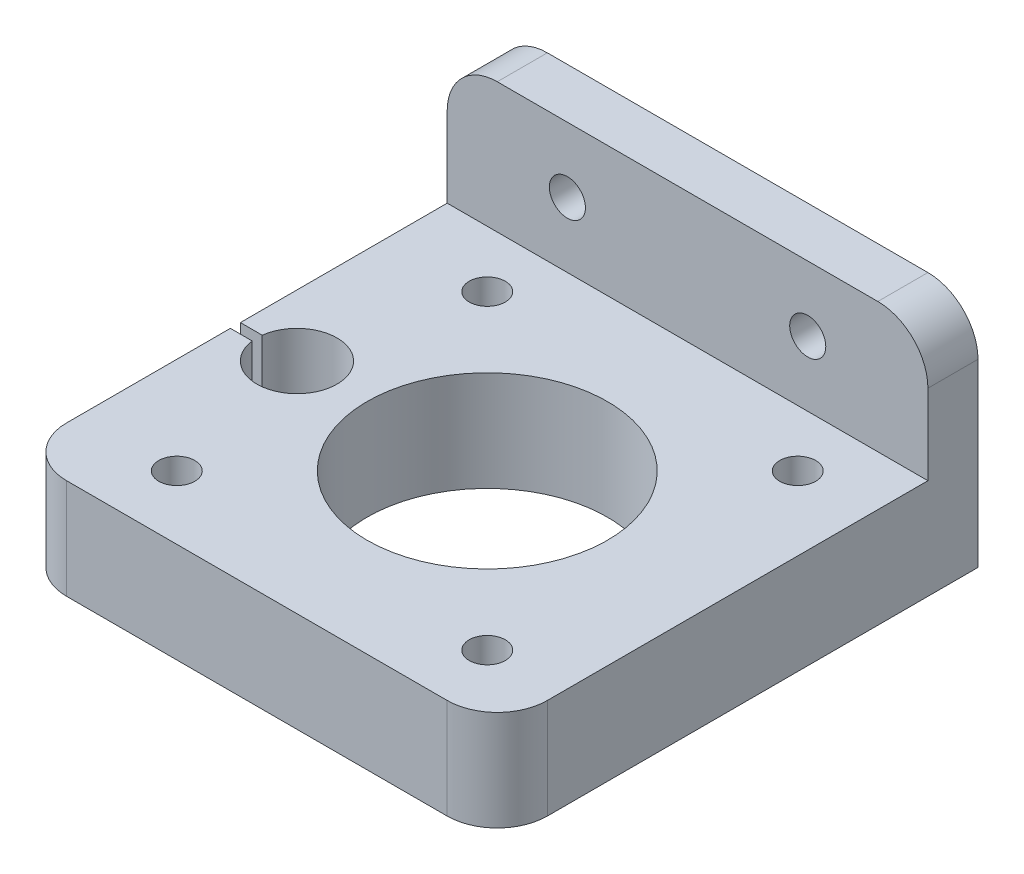
SolidWorks part; units mm, degrees
ref_plane "Front Plane" through (0, 0, 0) normal (0, 0, 1) x (1, 0, 0)
ref_plane "Top Plane" through (0, 0, 0) normal (0, 1, 0) x (1, 0, 0)
ref_plane "Right Plane" through (0, 0, 0) normal (1, 0, 0) x (0, 0, -1)
sketch "Sketch1" plane through (0, 0, 0) normal (0, 1, 0) x (1, 0, 0)
  line L0 (25.15, -26.15) -> (6.15, -26.15) construction
  line L1 (0, 0) -> (48, 0)
  line L2 (0, 0) -> (0, -48)
  line L3 (0, -48) -> (48, -48)
  line L4 (48, 0) -> (48, -48)
  line L5 (40.65, -10.65) -> (9.65, -10.65) construction
  line L6 (9.65, -10.65) -> (9.65, -41.65) construction
  line L7 (9.65, -41.65) -> (40.65, -41.65) construction
  line L8 (40.65, -41.65) -> (40.65, -10.65) construction
  line L9 (0, -25.65) -> (2.1814, -25.65)
  line L10 (2.1814, -25.65) -> (2.1814, -26.65)
  line L11 (2.1814, -26.65) -> (0, -26.65)
  line L12 (2.1814, -26.15) -> (6.15, -26.15) construction
  circle A1 centre (6.15, -26.15) radius 4
  circle A2 centre (25.15, -26.15) radius 12
  circle A5 centre (9.65, -10.65) radius 1.8
  circle A6 centre (9.65, -41.65) radius 1.8
  circle A7 centre (40.65, -41.65) radius 1.8
  circle A8 centre (40.65, -10.65) radius 1.8
  point P22 (0, 0)
  point P23 (7.2533, -26.15)
  dimension "D3" = 8
  dimension "D4" = 24
  dimension "D6" = 3.5
  dimension "D7" = 22.85
  dimension "D8" = 3.6
  dimension "D10" = 6.35
  dimension "D1" = 48
  dimension "D2" = 48
  dimension "D5" = 21.85
  dimension "D9" = 31
  dimension "D11" = 7.35
  dimension "D12" = 1
extrude "Boss-Extrude1" add sketch "Sketch1" along normal blind 10 contours L4 L1 L2 L3 region at (24, 0, 0.6788)
sketch "Sketch2" plane through (0, 0, 0) normal (-1, 0, 0) x (0, 0, 1)
  line L1 (0, 10) -> (5, 10)
  line L2 (0, 10) -> (0, 23)
  line L3 (0, 23) -> (5, 23)
  line L4 (5, 10) -> (5, 23)
  dimension "D1" = 13
  dimension "D2" = 5
extrude "Boss-Extrude2" add sketch "Sketch2" against normal up to surface (48 mm away) up to face at (48, 5, 24)
sketch "Sketch3" plane through (0, 0, 5) normal (0, 0, 1) x (1, 0, 0)
  line L0 (0, 16.5) -> (12, 16.5) construction
  line L1 (0, 10) -> (0, 23) construction
  line L2 (48, 16.5) -> (36, 16.5) construction
  line L3 (48, 10) -> (48, 23) construction
  circle A0 centre (36, 16.5) radius 1.8
  circle A1 centre (12, 16.5) radius 1.8
  dimension "D1" = 3.6
  dimension "D2" = 12
extrude "Cut-Extrude1" cut sketch "Sketch3" against normal blind 10
fillet "Fillet1" radius 5 4 edges at (48, 5, 48) (0, 5, 48) (48, 23, 2.5) (0, 23, 2.5)
